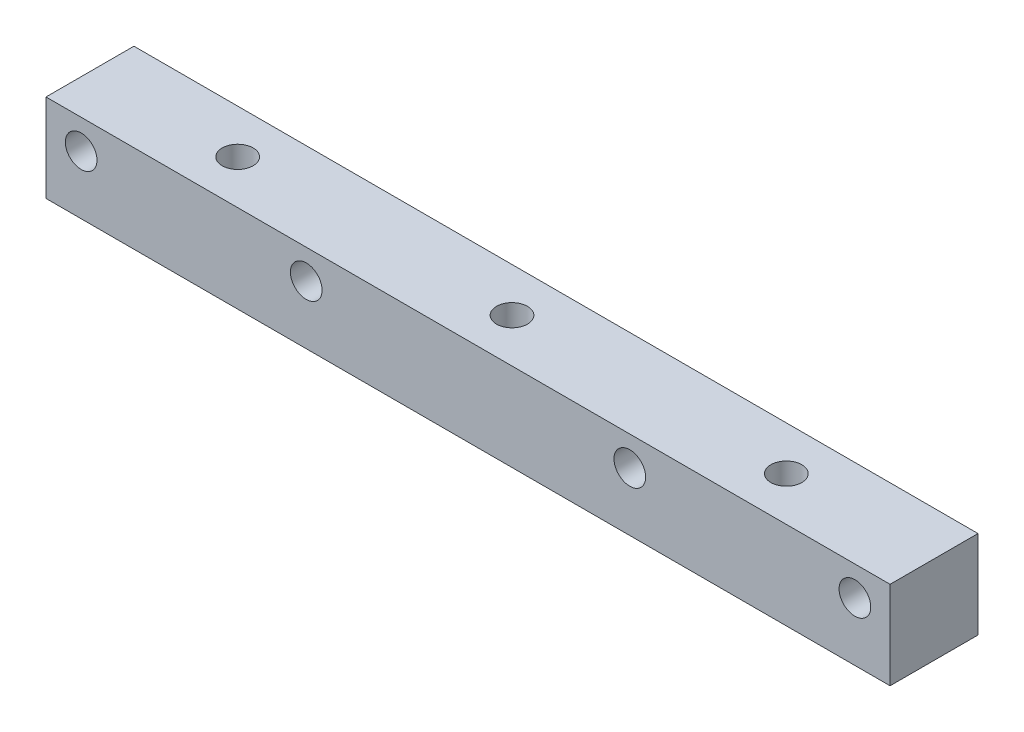
SolidWorks part; units mm, degrees
material "6061 Alloy"
ref_plane "Front Plane" through (0, 0, 0) normal (0, 0, 1) x (1, 0, 0)
ref_plane "Top Plane" through (0, 0, 0) normal (0, 1, 0) x (1, 0, 0)
ref_plane "Right Plane" through (0, 0, 0) normal (1, 0, 0) x (0, 0, -1)
sketch "Sketch1" plane through (0, 0, 0) normal (1, 0, 0) x (0, 0, -1)
  line L1 (-6.25, -6.25) -> (6.25, -6.25)
  line L2 (-6.25, -6.25) -> (-6.25, 6.25)
  line L3 (-6.25, 6.25) -> (6.25, 6.25)
  line L4 (6.25, -6.25) -> (6.25, 6.25)
  line L5 (-6.25, -6.25) -> (6.25, 6.25) construction
  line L6 (-6.25, 6.25) -> (6.25, -6.25) construction
  point P0 (0, 0)
  dimension "D1" = 12.5
extrude "Boss-Extrude1" add sketch "Sketch1" along normal mid plane 120
hole_wizard "Ø4.0mm Dowel Hole1" positions "Sketch2" profile "Sketch3" hole size "Ø4.0" standard "ANSI Metric" end condition through all
sketch "Sketch2" plane through (0, 0, 6.25) normal (0, 0, 1) x (1, 0, 0)
  line L0 (-55, 2.07) -> (-23, 2.07) construction
  line L1 (-23, 2.07) -> (23, 2.07) construction
  line L2 (23, 2.07) -> (55, 2.07) construction
  line L5 (-60, 6.25) -> (-60, -6.25) construction
  line L6 (60, -6.25) -> (-60, -6.25) construction
  line L7 (60, 6.25) -> (60, -6.25) construction
  point P0 (-55, 2.07)
  point P2 (-23, 2.07)
  point P4 (23, 2.07)
  point P6 (55, 2.07)
  dimension "D1" = 32
  dimension "D2" = 5
  dimension "D3" = 8.32
  dimension "D4" = 5
sketch "Sketch3" plane through (-55, 2.07, 6.25) normal (1, 0, 0) x (0, -1, 0)
  line L0 (0, 0) -> (0, 12.5)
  line L1 (0, 12.5) -> (2.25, 12.5)
  line L2 (2.25, 12.5) -> (2.25, 0)
  line L5 (2.25, 0) -> (0, 0)
  line L11 (0, -6.35) -> (0, 107.95) construction
  dimension "Thru Hole Dia." = 4.5
  dimension "Thru Hole Depth" = 12.5
hole_wizard "Ø1.0mm Dowel Hole1" positions "Sketch4" profile "Sketch5" hole size "Ø1.0" standard "ANSI Metric" end condition through all
sketch "Sketch4" plane through (0, 6.25, 0) normal (0, 1, 0) x (1, 0, 0)
  line L0 (-60, 6.25) -> (-60, -6.25) construction
  line L1 (60, 6.25) -> (60, -6.25) construction
  point P0 (-39, 0)
  point P2 (0, 0)
  point P5 (39, 0)
  dimension "D1" = 21
  dimension "D2" = 21
sketch "Sketch5" plane through (-39, 6.25, 0) normal (1, 0, 0) x (0, 0, 1)
  line L0 (0, 0) -> (0, 12.5)
  line L1 (0, 12.5) -> (2.2, 12.5)
  line L2 (2.2, 12.5) -> (2.2, 0)
  line L5 (2.2, 0) -> (0, 0)
  line L11 (0, -6.35) -> (0, 107.95) construction
  dimension "Thru Hole Dia." = 4.4
  dimension "Thru Hole Depth" = 12.5
equation "\"D1@Sketch4\"=(32/2)+5"
equation "\"D2@Sketch4\"=\"D1@Sketch4\""
